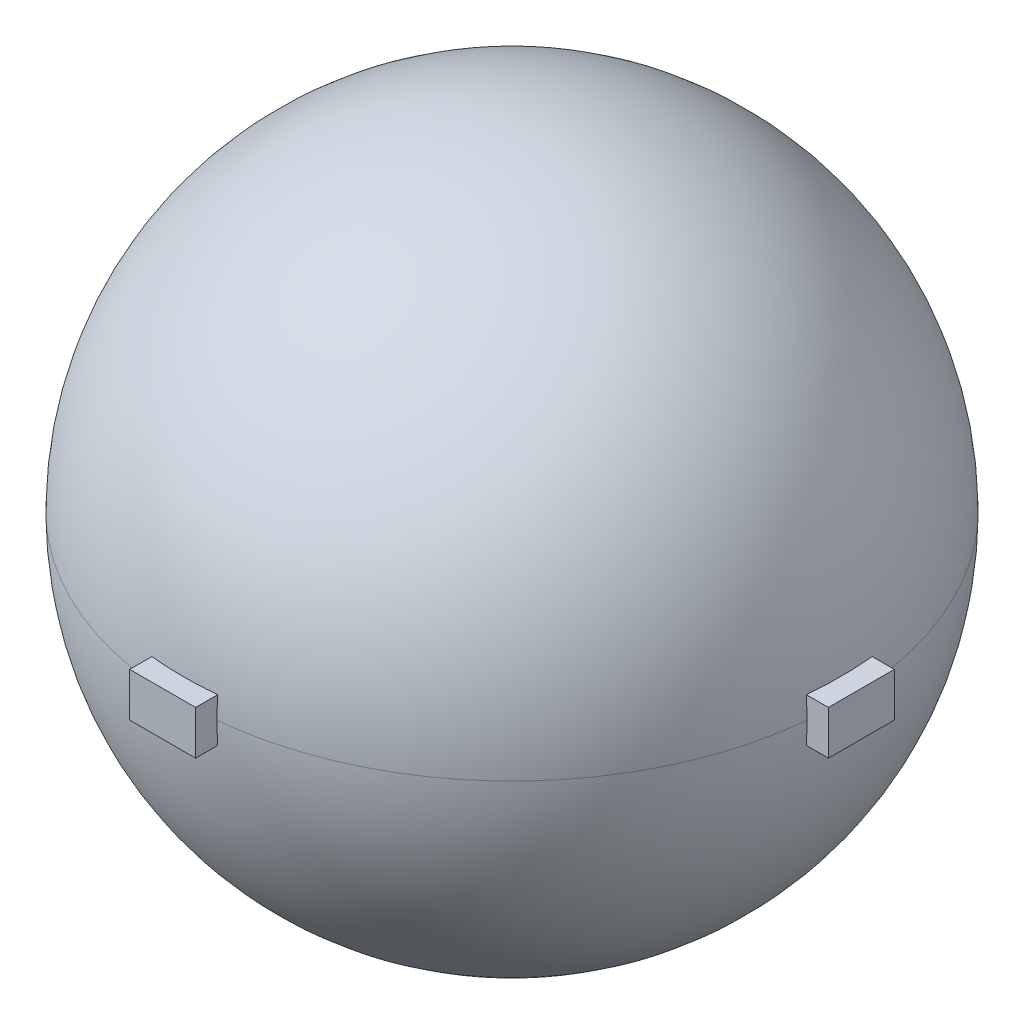
SolidWorks part; units mm, degrees
ref_plane "Front Plane" through (0, 0, 0) normal (0, 0, 1) x (1, 0, 0)
ref_plane "Top Plane" through (0, 0, 0) normal (0, 1, 0) x (1, 0, 0)
ref_plane "Right Plane" through (0, 0, 0) normal (1, 0, 0) x (0, 0, -1)
sketch "Sketch1" plane through (0, 0, 0) normal (0, 1, 0) x (1, 0, 0)
  circle A0 centre (0, 0) radius 381
  dimension "D1" = 762
extrude "Boss-Extrude1" add sketch "Sketch1" along normal blind 762
fillet "Fillet1" radius 381 2 edges at (0, 0, 381) (0, 762, 381)
shell "Shell2" thickness 3.175
ref_plane "Plane3" through (0, 381, 0) normal (0, 1, 0) x (1, 0, 0)
ref_plane "Plane4" through (403.86, 0, 0) normal (1, 0, 0) x (0, 0, -1)
sketch "Sketch4" plane through (403.86, 0, 0) normal (1, 0, 0) x (0, 0, -1)
  line L0 (419.1, 381) -> (-419.1, 381) construction
  line L1 (-38.1, 355.6) -> (38.1, 355.6)
  line L2 (-38.1, 355.6) -> (-38.1, 406.4)
  line L3 (-38.1, 406.4) -> (38.1, 406.4)
  line L4 (38.1, 355.6) -> (38.1, 406.4)
  line L5 (-38.1, 355.6) -> (38.1, 406.4) construction
  line L6 (-38.1, 406.4) -> (38.1, 355.6) construction
  point P0 (0, 381)
  dimension "D1" = 50.8
  dimension "D2" = 76.2
extrude "Boss-Extrude3" add sketch "Sketch4" against normal up to surface (25.6217 mm away) up to face at (0, 381, -381)
mirror "Mirror2" about plane through (0, 0, 0) normal (1, 0, 0) of "Boss-Extrude3"
ref_plane "Plane5" through (0, 0, 403.86) normal (0, 0, 1) x (1, 0, 0)
sketch "Sketch5" plane through (0, 0, 403.86) normal (0, 0, 1) x (1, 0, 0)
  line L0 (379.0902, 381) -> (-379.0902, 381) construction
  line L1 (-38.1, 355.6) -> (38.1, 355.6)
  line L2 (-38.1, 355.6) -> (-38.1, 406.4)
  line L3 (-38.1, 406.4) -> (38.1, 406.4)
  line L4 (38.1, 355.6) -> (38.1, 406.4)
  line L5 (-38.1, 355.6) -> (38.1, 406.4) construction
  line L6 (-38.1, 406.4) -> (38.1, 355.6) construction
  point P0 (0, 381)
  dimension "D1" = 50.8
  dimension "D2" = 76.2
extrude "Boss-Extrude4" add sketch "Sketch5" against normal up to surface (25.6217 mm away) up to face at (0, 368.2964, 0)
mirror "Mirror3" about plane through (0, 0, 0) normal (0, 0, 1) of "Boss-Extrude4"
